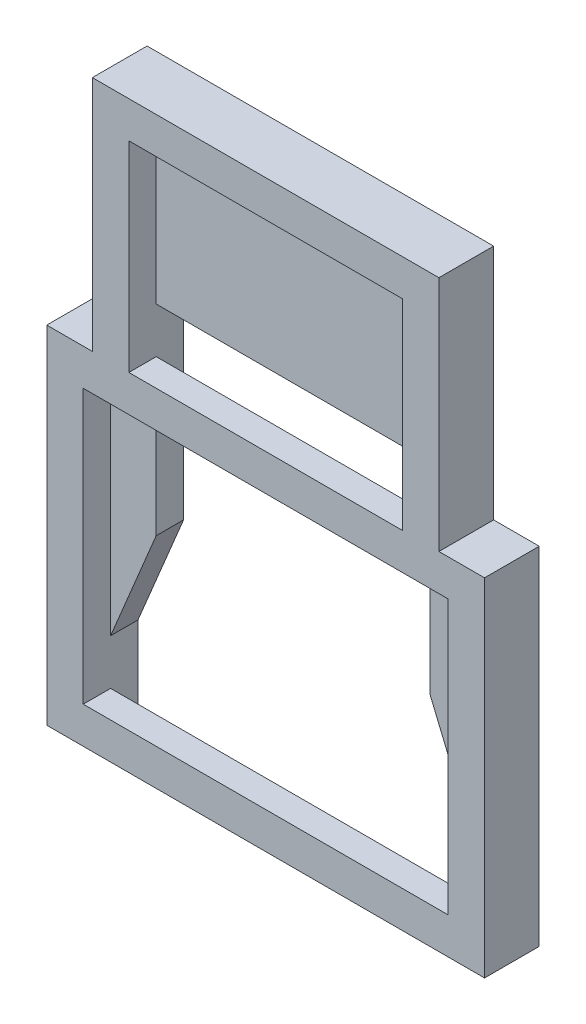
SolidWorks part; units mm, degrees
ref_plane "Plano frontal" through (0, 0, 0) normal (0, 0, 1) x (1, 0, 0)
ref_plane "Plano superior" through (0, 0, 0) normal (0, 1, 0) x (1, 0, 0)
ref_plane "Plano direito" through (0, 0, 0) normal (1, 0, 0) x (0, 0, -1)
sketch "Esboço1" plane through (0, 0, 0) normal (0, 0, 1) x (1, 0, 0)
  line L0 (0, 0) -> (10, 0)
  line L1 (10, 0) -> (10, 15)
  line L2 (10, 15) -> (-10, 15)
  line L3 (-10, 15) -> (-10, 0)
  line L4 (-10, 0) -> (0, 0)
  line L5 (-12, -2) -> (0, -2)
  line L6 (0, -2) -> (12, -2)
  line L7 (12, -2) -> (12, 17)
  line L8 (12, 17) -> (9.5, 17)
  line L9 (-12, 17) -> (-12, -2)
  line L10 (0, 0) -> (0, 17)
  line L11 (0, 17) -> (0, 28)
  line L12 (-7.5, 28) -> (7.5, 28)
  line L13 (7.5, 28) -> (7.5, 17)
  line L14 (-7.5, 28) -> (-7.5, 17)
  line L15 (9.5, 30) -> (9.5, 17)
  line L16 (-9.5, 30) -> (9.5, 30)
  line L17 (-9.5, 30) -> (-9.5, 17)
  line L18 (7.5, 17) -> (-7.5, 17)
  line L19 (-10, 2.5) -> (0, 2.5)
  line L20 (0, 2.5) -> (10, 2.5)
  line L21 (7.5, 19.5) -> (-7.5, 19.5)
  line L22 (-9.5, 17) -> (-12, 17)
  line L23 (12, 17) -> (-12, 17) construction
  line L24 (0, 8.5) -> (10, 8.5)
  line L25 (7.5, 28) -> (7.5, 17) construction
  line L26 (10, 2.5) -> (7.5, 8.5)
  line L27 (7.5, 17) -> (7.5, 8.5)
  line L28 (-10, 2.5) -> (-7.5, 8.5)
  line L29 (-7.5, 17) -> (-7.5, 8.5)
  line L30 (-10, 0) -> (-10, -2)
  line L31 (-10, -2) -> (10, -2)
  line L32 (10, -2) -> (10, 0)
  point P21 (12, 19.5)
  point P22 (-12, 19.5)
  dimension "D1" = 2
  dimension "D2" = 2
  dimension "D4" = 2.5
extrude "Ressalto-extrusão1" add sketch "Esboço1" along normal blind 1.5 contours L27 L18 L10 L2 | L18 L29 L2 L10 | L32 L6 L7 L8 L15 L16 L17 L22 L9 L5 L30 L3 L2 L29 L14 L12 L13 L27 L1 | L6 L32 L0 L4 L30 L5 region at (0, -1, 0) region at (10.4, 1.25, 0) region at (3.75, 16, 0) region at (-3.75, 16, 0)
extrude "Ressalto-extrusão2" add sketch "Esboço1<4>" against normal blind 1.5 contours L17 L22 L9 L5 L6 L7 L8 L15 L16 L29 L14 L12 L13 L27 L2 L1 L0 L4 L3 | L21 L11 L12 L14 | L21 L13 L12 L11 | L2 L27 L24 L1 | L26 L1 L24 | L29 L2 L3 L28 region at (10.4, 1.25, 0) region at (9.1667, 6.5, 0) region at (-8.8816, 10.0921, 0) region at (8.75, 11.75, 0) region at (-3.75, 23.75, 0) region at (3.75, 23.75, 0)
sketch "Esboço1<4>" plane through (0, 0, 0) normal (0, 0, 1) x (1, 0, 0) same geometry as "Esboço1"
